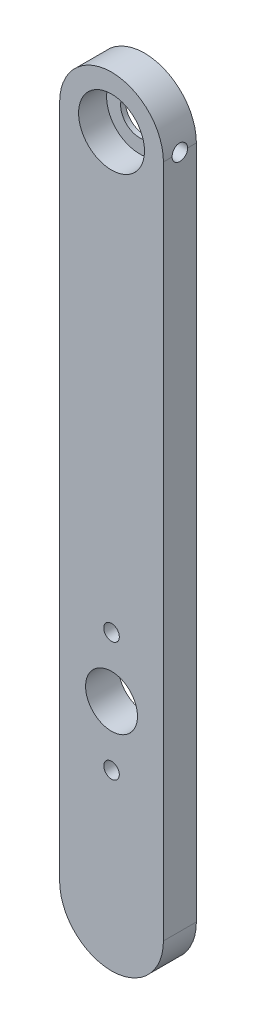
SolidWorks part; units mm, degrees
ref_plane "Alzado" through (0, 0, 0) normal (0, 0, 1) x (1, 0, 0)
ref_plane "Planta" through (0, 0, 0) normal (0, 1, 0) x (1, 0, 0)
ref_plane "Vista lateral" through (0, 0, 0) normal (1, 0, 0) x (0, 0, -1)
sketch "Croquis1" plane through (0, 0, 0) normal (0, 0, 1) x (1, 0, 0)
  line L0 (0, 65) -> (0, -65) construction
  line L1 (10, 65) -> (10, -65)
  line L2 (-10, 65) -> (-10, -65)
  arc A0 (10, 65) -> (-10, 65) centre (0, 65) ccw
  arc A1 (-10, -65) -> (10, -65) centre (0, -65) ccw
  point P2 (0, 0)
  point P8 (0, 75)
  point P9 (0, -75)
  dimension "D1" = 150
  dimension "D2" = 20
extrude "Saliente-Extruir1" add sketch "Croquis1" along normal blind 6.35
sketch "Croquis2" plane through (0, 0, 6.35) normal (0, 0, 1) x (1, 0, 0)
  circle A0 centre (0, 65) radius 6.35
  dimension "D1" = 12.7
extrude "Cortar-Extruir1" cut sketch "Croquis2" against normal blind 5.4
sketch "Croquis3" plane through (0, 0, 0.95) normal (0, 0, 1) x (1, 0, 0)
  circle A0 centre (0, 65) radius 3.65
  dimension "D1" = 7.3
extrude "Cortar-Extruir2" cut sketch "Croquis3" against normal blind 5.4
sketch "Croquis4" plane through (0, 0, 6.35) normal (0, 0, 1) x (1, 0, 0)
  circle A0 centre (0, -30) radius 5
  circle A1 centre (0, -18.5) radius 1.5
  circle A2 centre (0, -41.5) radius 1.5
  point P2 (0, 65)
  point P8 (0, -20)
  point P9 (0, -25)
  point P10 (0, -35)
  point P11 (0, -40)
  dimension "D2" = 10
  dimension "D5" = 3
  dimension "D6" = 3
  dimension "D1" = 95
  dimension "D3" = 5
  dimension "D4" = 5
extrude "Cortar-Extruir3" cut sketch "Croquis4" against normal through all
sketch "Croquis5" plane through (10, 0, 0) normal (1, 0, 0) x (0, 0, -1)
  line L0 (-6.35, 65) -> (0, 65) construction
  circle A0 centre (-3.175, 65) radius 1.5
  dimension "D1" = 3
extrude "Cortar-Extruir4" cut sketch "Croquis5" against normal blind 10
ref_axis "Eje1" through (0, 65, 0.95) along (0, 0, 1)
